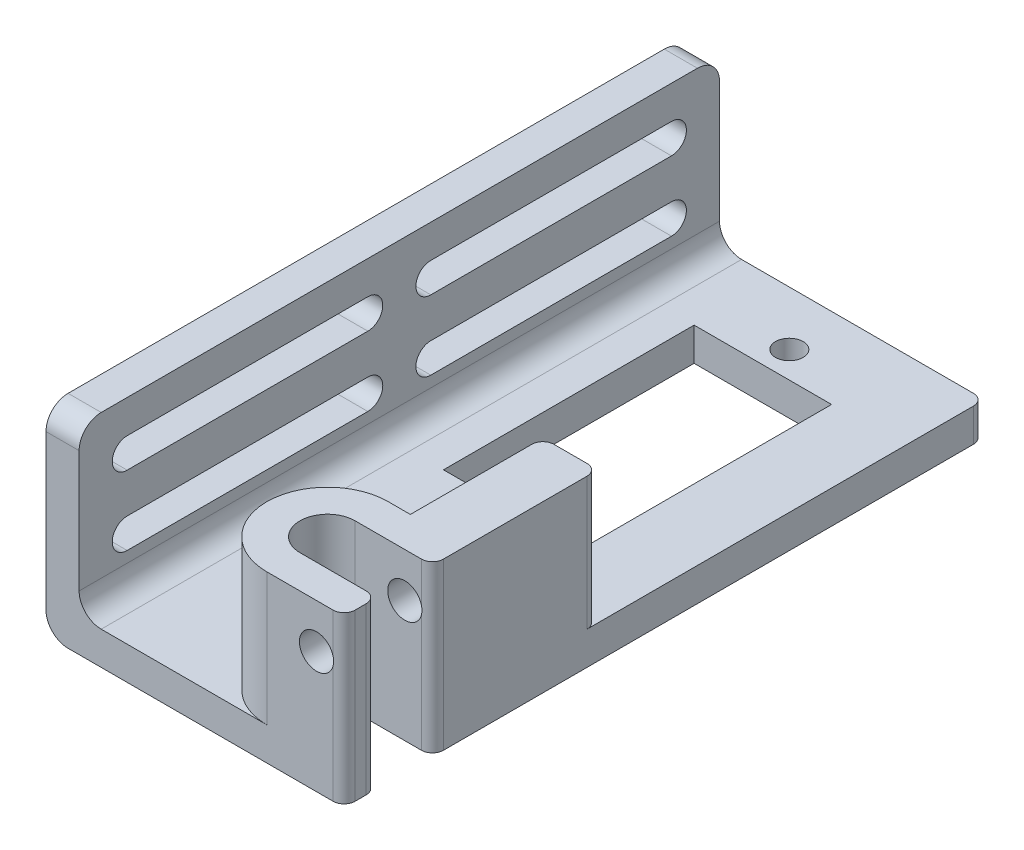
SolidWorks part; units mm, degrees
ref_plane "Front Plane" through (0, 0, 0) normal (0, 0, 1) x (1, 0, 0)
ref_plane "Top Plane" through (0, 0, 0) normal (0, 1, 0) x (1, 0, 0)
ref_plane "Right Plane" through (0, 0, 0) normal (1, 0, 0) x (0, 0, -1)
sketch "Sketch1" plane through (0, 0, 0) normal (0, 1, 0) x (1, 0, 0)
  line L0 (27, 8) -> (20, 8)
  line L1 (0, 0) -> (27, 0)
  line L2 (0, 0) -> (0, 58)
  line L3 (0, 58) -> (27, 58)
  line L4 (27, 0) -> (27, 3)
  line L5 (27, 3) -> (20, 3)
  line L6 (20, 8) -> (20, 3) construction
  line L7 (27, 8) -> (27, 58)
  arc A0 (20, 3) -> (20, 8) centre (20, 5.5) cw
  dimension "D1" = 58
  dimension "D2" = 27
  dimension "D3" = 5
  dimension "D4" = 3
  dimension "D5" = 7
extrude "Boss-Extrude1" add sketch "Sketch1" along normal blind 3
sketch "Sketch2" plane through (0, 3, 0) normal (0, 1, 0) x (1, 0, 0)
  line L0 (0, 58) -> (0, 0) construction
  line L1 (8, 50.7) -> (20.45, 50.7)
  line L2 (8, 50.7) -> (8, 28)
  line L3 (8, 28) -> (20.45, 28)
  line L4 (20.45, 50.7) -> (20.45, 28)
  line L5 (0, 0) -> (27, 0) construction
  line L6 (14.225, 50.7) -> (14.225, 58) construction
  line L7 (27, 58) -> (0, 58) construction
  circle A1 centre (14.225, 53.1) radius 1.25
  circle A2 centre (14.225, 25.6) radius 1.25
  point P12 (11.225, 40.2)
  dimension "D4" = 2.5
  dimension "D5" = 2.5
  dimension "D1" = 12.45
  dimension "D2" = 22.7
  dimension "D3" = 8
  dimension "D6" = 2.4
  dimension "D7" = 2.4
  dimension "D8" = 28
extrude "Cut-Extrude1" cut sketch "Sketch2" against normal blind 3
sketch "Sketch3" plane through (0, 3, 0) normal (0, 1, 0) x (1, 0, 0)
  line L0 (0, 0) -> (27, 0) construction
  line L1 (0, 58) -> (3, 58)
  line L2 (0, 58) -> (0, 0)
  line L3 (0, 0) -> (3, 0)
  line L4 (3, 58) -> (3, 0)
  dimension "D1" = 3
extrude "Boss-Extrude2" add sketch "Sketch3" along normal blind 15
sketch "Sketch4" plane through (0, 3, 0) normal (0, 1, 0) x (1, 0, 0)
  line L0 (3, 0) -> (27, 0) construction
  line L1 (20, 11) -> (22, 11)
  line L2 (27, 8) -> (27, 58) construction
  line L3 (20, 8) -> (27, 8) construction
  line L4 (20, 0) -> (27, 0)
  line L5 (27, 0) -> (27, 3)
  line L6 (27, 3) -> (20, 3)
  line L7 (27, 11) -> (27, 8)
  line L8 (27, 8) -> (20, 8)
  line L11 (27, 11) -> (27, 23)
  line L12 (27, 23) -> (22, 23)
  line L13 (22, 11) -> (22, 23)
  arc A0 (20, 0) -> (20, 11) centre (20, 5.5) cw
  arc A1 (20, 8) -> (20, 3) centre (20, 5.5) ccw construction
  arc A2 (20, 8) -> (20, 3) centre (20, 5.5) ccw
  dimension "D1" = 3
  dimension "D2" = 3
  dimension "D3" = 5
  dimension "D4" = 12
extrude "Boss-Extrude3" add sketch "Sketch4" along normal blind 12
fillet "Fillet1" radius 2 2 edges at (3, 3, -29) (0, 0, -29)
fillet "Fillet2" radius 2 2 edges at (1.5, 18, -58) (1.5, 18, 0)
fillet "Fillet3" radius 1 6 edges at (27, 9, -23) (22, 9, -23) (27, 7.5, -8) (27, 7.5, -3) (27, 7.5, 0) (27, 1.5, -58)
sketch "Sketch5" plane through (0, 0, 0) normal (-1, 0, 0) x (0, 0, 1)
  line L0 (-53.65, 13.65) -> (-31.85, 13.65) construction
  line L1 (-53.65, 15) -> (-31.85, 15)
  line L2 (-53.65, 12.3) -> (-31.85, 12.3)
  line L3 (-53.65, 7.35) -> (-31.85, 7.35) construction
  line L4 (-53.65, 8.7) -> (-31.85, 8.7)
  line L5 (-53.65, 6) -> (-31.85, 6)
  line L6 (-56, 18) -> (-2, 18) construction
  line L7 (-58, 2) -> (0, 2) construction
  line L8 (-26.15, 13.65) -> (-4.35, 13.65) construction
  line L9 (-26.15, 15) -> (-4.35, 15)
  line L10 (-26.15, 12.3) -> (-4.35, 12.3)
  line L11 (-26.15, 7.35) -> (-4.35, 7.35) construction
  line L12 (-26.15, 8.7) -> (-4.35, 8.7)
  line L13 (-26.15, 6) -> (-4.35, 6)
  line L14 (-58, 16) -> (-58, 2) construction
  line L15 (0, 16) -> (0, 2) construction
  line L16 (-29, 18) -> (-29, 2) construction
  arc A0 (-53.65, 15) -> (-53.65, 12.3) centre (-53.65, 13.65) ccw
  arc A1 (-31.85, 12.3) -> (-31.85, 15) centre (-31.85, 13.65) ccw
  arc A2 (-53.65, 8.7) -> (-53.65, 6) centre (-53.65, 7.35) ccw
  arc A3 (-31.85, 6) -> (-31.85, 8.7) centre (-31.85, 7.35) ccw
  arc A4 (-26.15, 15) -> (-26.15, 12.3) centre (-26.15, 13.65) ccw
  arc A5 (-4.35, 12.3) -> (-4.35, 15) centre (-4.35, 13.65) ccw
  arc A6 (-26.15, 8.7) -> (-26.15, 6) centre (-26.15, 7.35) ccw
  arc A7 (-4.35, 6) -> (-4.35, 8.7) centre (-4.35, 7.35) ccw
  point P2 (-42.75, 13.65)
  point P9 (-42.75, 7.35)
  point P20 (-15.25, 13.65)
  point P25 (-15.25, 7.35)
  point P34 (-55, 13.65)
  point P35 (-55, 7.35)
  point P36 (-3, 13.65)
  point P39 (-3, 7.35)
  point P40 (-30.5, 13.65)
  point P41 (-30.5, 7.35)
  point P42 (-27.5, 13.65)
  point P43 (-27.5, 7.35)
  dimension "D8" = 3
  dimension "D1" = 2.7
  dimension "D2" = 2.7
  dimension "D3" = 3
  dimension "D4" = 4
  dimension "D5" = 2.7
  dimension "D6" = 2.7
  dimension "D7" = 3
  dimension "D9" = 3
  dimension "D10" = 3
  dimension "D11" = 1.5
  dimension "D12" = 1.5
  dimension "D13" = 1.5
  dimension "D14" = 1.5
extrude "Cut-Extrude2" cut sketch "Sketch5" against normal blind 3
sketch "Sketch7" plane through (0, 0, -23) normal (0, 0, -1) x (-1, 0, 0)
  line L0 (-24.5, 15) -> (-24.5, 3) construction
  line L1 (-26, 15) -> (-23, 15) construction
  line L2 (-26, 3) -> (-23, 3) construction
  circle A0 centre (-24.5, 11) radius 1.55
  dimension "D1" = 3.1
  dimension "D2" = 4
extrude "Cut-Extrude3" cut sketch "Sketch7" against normal through all
